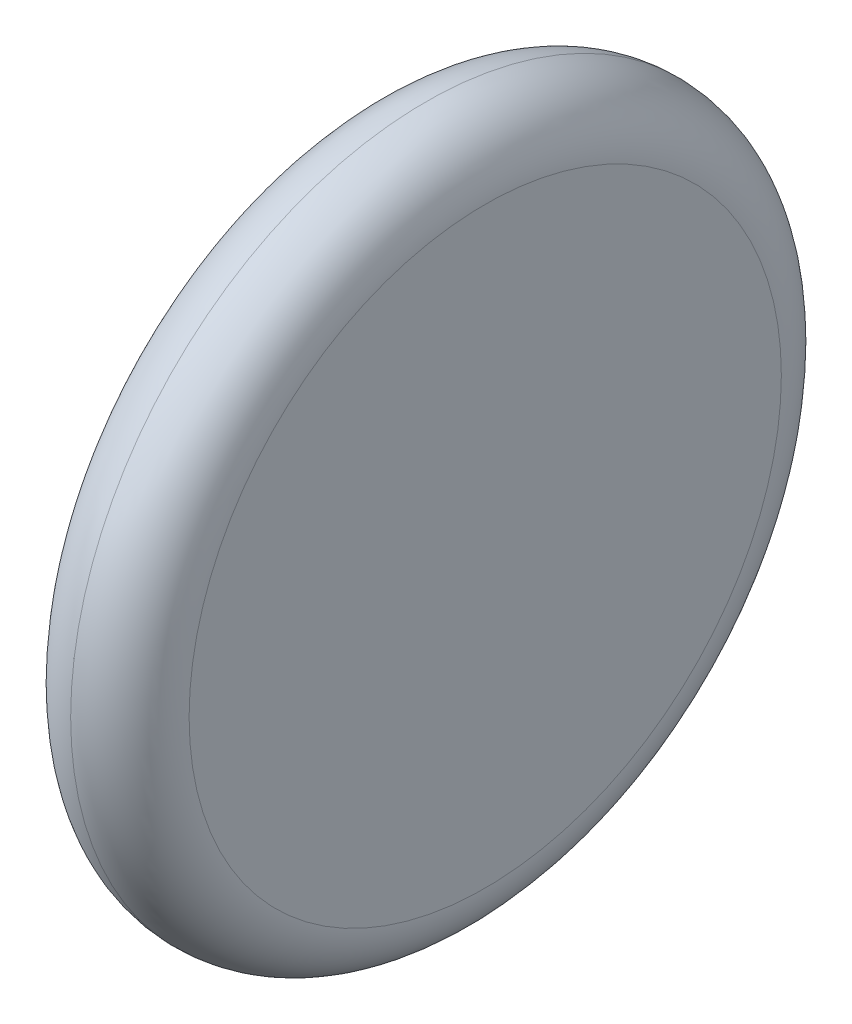
SolidWorks part; units mm, degrees
ref_plane "前视基准面" through (0, 0, 0) normal (0, 0, 1) x (1, 0, 0)
ref_plane "上视基准面" through (0, 0, 0) normal (0, 1, 0) x (1, 0, 0)
ref_plane "右视基准面" through (0, 0, 0) normal (1, 0, 0) x (0, 0, -1)
sketch "草图1" plane through (0, 0, 0) normal (1, 0, 0) x (0, 0, -1)
  circle A0 centre (0, 0) radius 90
extrude "凸台-拉伸1" add sketch "草图1" along normal blind 30
fillet "圆角1" radius 15 2 edges at (0, 0, -90) (30, 0, -90)
